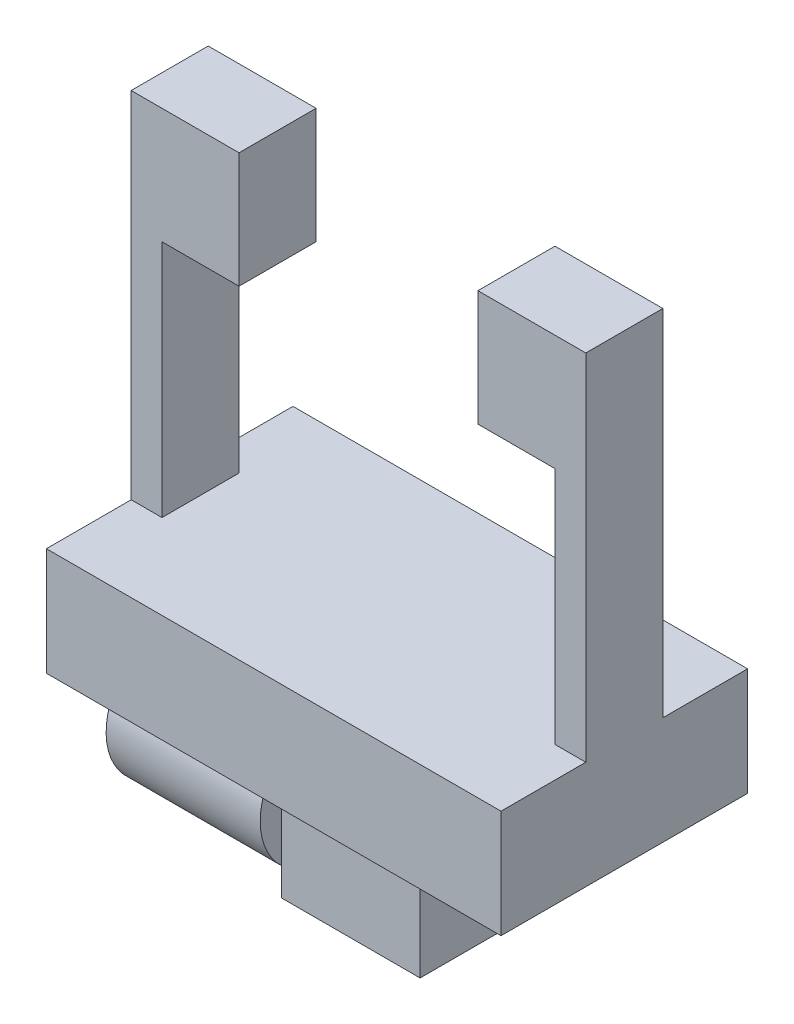
SolidWorks part; units mm, degrees
material "6061-T6 (SS)"
ref_plane "Front Plane" through (0, 0, 0) normal (0, 0, 1) x (1, 0, 0)
ref_plane "Top Plane" through (0, 0, 0) normal (0, 1, 0) x (1, 0, 0)
ref_plane "Right Plane" through (0, 0, 0) normal (1, 0, 0) x (0, 0, -1)
sketch "Sketch1" plane through (0, 0, 0) normal (0, 0, 1) x (1, 0, 0)
  line L1 (-37.465, -8.89) -> (37.465, -8.89)
  line L2 (-37.465, -8.89) -> (-37.465, 8.89)
  line L3 (-37.465, 8.89) -> (37.465, 8.89)
  line L4 (37.465, -8.89) -> (37.465, 8.89)
  line L5 (-37.465, -8.89) -> (37.465, 8.89) construction
  line L6 (-37.465, 8.89) -> (37.465, -8.89) construction
  point P0 (0, 0)
  dimension "D1" = 74.93
extrude "Boss-Extrude1" add sketch "Sketch1" along normal mid plane 40.64
sketch "Sketch2" plane through (0, 0, 0) normal (0, 0, 1) x (1, 0, 0)
  line L1 (-37.465, 8.89) -> (-32.385, 8.89)
  line L2 (-37.465, 8.89) -> (-37.465, 48.26)
  line L3 (-37.465, 48.26) -> (-32.385, 48.26)
  line L4 (-32.385, 8.89) -> (-32.385, 48.26)
  line L5 (37.465, 8.89) -> (32.385, 8.89)
  line L6 (37.465, 8.89) -> (37.465, 48.26)
  line L7 (37.465, 48.26) -> (32.385, 48.26)
  line L8 (32.385, 8.89) -> (32.385, 48.26)
  dimension "D2" = 39.37
  dimension "D3" = 5.08
  dimension "D4" = 39.37
extrude "Boss-Extrude2" add sketch "Sketch2" along normal mid plane 12.7
sketch "Sketch3" plane through (0, 0, 0) normal (0, 0, 1) x (1, 0, 0)
  line L1 (37.465, 48.26) -> (19.685, 48.26)
  line L2 (37.465, 48.26) -> (37.465, 67.31)
  line L3 (37.465, 67.31) -> (19.685, 67.31)
  line L4 (19.685, 48.26) -> (19.685, 67.31)
  line L5 (-37.465, 48.26) -> (-19.685, 48.26)
  line L6 (-37.465, 48.26) -> (-37.465, 67.31)
  line L7 (-37.465, 67.31) -> (-19.685, 67.31)
  line L8 (-19.685, 48.26) -> (-19.685, 67.31)
  dimension "D1" = 17.78
  dimension "D2" = 19.05
  dimension "D3" = 17.78
  dimension "D4" = 19.05
extrude "Boss-Extrude3" add sketch "Sketch3" along normal mid plane 12.7
sketch "Sketch5" plane through (0, 0, 0) normal (0, 0, 1) x (1, 0, 0)
  line L0 (-37.465, -8.89) -> (37.465, -8.89) construction
  line L1 (-11.43, -8.89) -> (11.43, -8.89)
  line L2 (-11.43, -8.89) -> (-11.43, -34.29)
  line L3 (-11.43, -34.29) -> (11.43, -34.29)
  line L4 (11.43, -8.89) -> (11.43, -34.29)
  point P4 (0, -8.89)
extrude "Boss-Extrude4" add sketch "Sketch5" along normal mid plane 15.24
sketch "Sketch6" plane through (-11.43, 0, 0) normal (-1, 0, 0) x (0, 0, 1)
  line L0 (-7.62, -8.89) -> (7.62, -34.29) construction
  circle A0 centre (0, -21.59) radius 11.1125
  dimension "D1" = 22.225
extrude "Boss-Extrude5" add sketch "Sketch6" along normal blind 25.4
equation "\"Base Length\"= 2.95in"
equation "\"Base Height\" = 0.7in"
equation "\"Support Width\"= 0.2in"
equation "\"Support Height\" = 1.55in"
equation "\"Lip Width\"= 0.7in"
equation "\"Lip Height\"= 0.75in"
equation "\"Stem Height\"= 1in"
equation "\"Stem Width\"= 0.9in"
equation "\"Bar Diameter\"= 0.875in"
equation "\"D1@Sketch1\"=\"Base Length\""
equation "\"D2@Sketch1\"=\"Base Height\""
equation "\"D1@Sketch2\"=\"Support Width\""
equation "\"D3@Sketch2\"=\"Support Width\""
equation "\"D2@Sketch2\"=\"Support Height\""
equation "\"D4@Sketch2\"=\"Support Height\""
equation "\"D3@Sketch3\"=\"Lip Width\""
equation "\"D1@Sketch3\"=\"Lip Width\""
equation "\"D4@Sketch3\"=\"Lip Height\""
equation "\"D2@Sketch3\"=\"Lip Height\""
equation "\"D1@Sketch5\"=\"Stem Width\""
equation "\"D2@Sketch5\"=\"Stem Height\""
equation "\"D1@Sketch6\"=\"Bar Diameter\""
equation "\"Base Depth\"= 1.6in"
equation "\"D1@Boss-Extrude1\"=\"Base Depth\""
equation "\"Support Depth\"= 0.5in"
equation "\"D1@Boss-Extrude2\"=\"Support Depth\""
equation "\"Lip Depth\"= 0.5in"
equation "\"D1@Boss-Extrude3\"=\"Lip Depth\""
equation "\"Stem Depth\"= 0.6in"
equation "\"D1@Boss-Extrude4\"=\"Stem Depth\""
equation "\"Bar Length\"= 1in"
equation "\"D1@Boss-Extrude5\"=\"Bar Length\""
